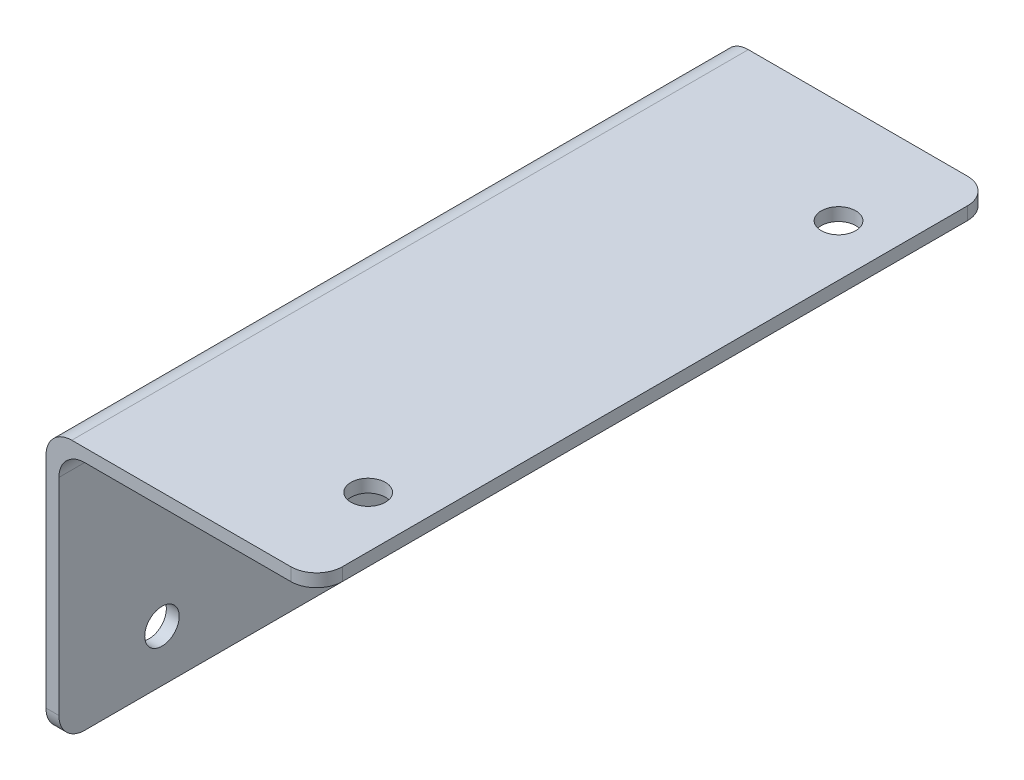
SolidWorks part; units mm, degrees
ref_plane "Front Plane" through (0, 0, 0) normal (0, 0, 1) x (1, 0, 0)
ref_plane "Top Plane" through (0, 0, 0) normal (0, 1, 0) x (1, 0, 0)
ref_plane "Right Plane" through (0, 0, 0) normal (1, 0, 0) x (0, 0, -1)
sketch "Sketch2" plane through (0, 0, 0) normal (0, 0, 1) x (1, 0, 0)
  line L1 (0, 0) -> (-1.27, 0)
  line L2 (0, 0) -> (0, 25.4)
  line L4 (-1.27, 0) -> (-1.27, 26.67)
  line L5 (-1.27, 26.67) -> (25.4, 26.67)
  line L7 (0, 25.4) -> (25.4, 25.4)
  line L8 (25.4, 26.67) -> (25.4, 25.4)
  dimension "D1" = 1.27
  dimension "D2" = 25.4
  dimension "D3" = 1.27
  dimension "D4" = 25.4
extrude "Boss-Extrude1" add sketch "Sketch2" along normal blind 66.675 contours L2 L7 L8 L5 L4 L1
sketch "Sketch3" plane through (-1.27, 0, 0) normal (-1, 0, 0) x (0, 0, 1)
  line L0 (33.3375, 0) -> (33.3375, 31.5293) construction
  line L1 (66.675, 0) -> (0, 0) construction
  circle A0 centre (10.16, 5.08) radius 1.7
  circle A1 centre (56.515, 5.08) radius 1.7
  dimension "D3" = 3.4
  dimension "D1" = 10.16
  dimension "D2" = 5.08
extrude "Cut-Extrude1" cut sketch "Sketch3" against normal through all
sketch "Sketch6" plane through (0, 26.67, 0) normal (0, 1, 0) x (1, 0, 0)
  line L0 (-1.27, -33.3375) -> (29.2999, -33.3375) construction
  line L1 (-1.27, -66.675) -> (-1.27, 0) construction
  circle A0 centre (20.32, -10.16) radius 1.7
  circle A1 centre (20.32, -56.515) radius 1.7
  dimension "D1" = 5.08
  dimension "D3" = 3.4
  dimension "D2" = 10.16
extrude "Cut-Extrude2" cut sketch "Sketch6" against normal through all
fillet "Fillet1" radius 2.54 4 edges at (25.4, 26.035, 0) (-0.635, 0, 0) (-0.635, 0, 66.675) (25.4, 26.035, 66.675)
fillet "Fillet2" radius 2.54 2 edges at (0, 25.4, 33.3375) (-1.27, 26.67, 33.3375)
